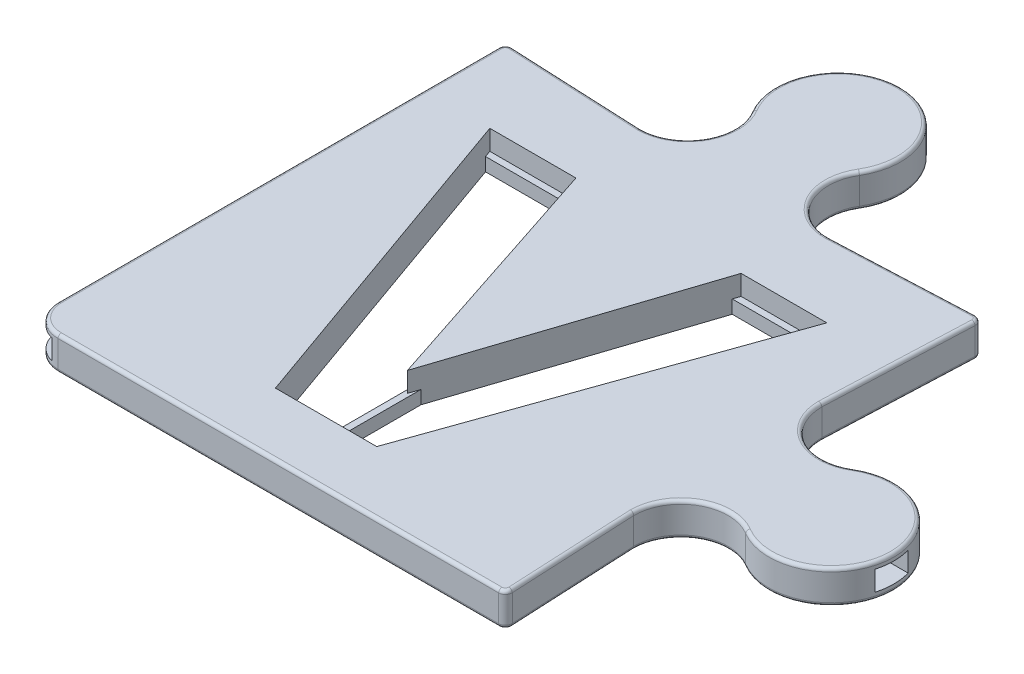
SolidWorks part; units mm, degrees
ref_plane "Front Plane" through (0, 0, 0) normal (0, 0, 1) x (1, 0, 0)
ref_plane "Top Plane" through (0, 0, 0) normal (0, 1, 0) x (1, 0, 0)
ref_plane "Right Plane" through (0, 0, 0) normal (1, 0, 0) x (0, 0, -1)
sketch "Sketch1" plane through (0, 0, 0) normal (0, 1, 0) x (1, 0, 0)
  line L0 (-31, -36) -> (37, -36) construction
  line L1 (-36, 37) -> (-36, -31) construction
  line L2 (-14.1421, 36) -> (-36, 37) construction
  line L3 (37, 37) -> (14.1421, 36) construction
  line L4 (36, 13.1421) -> (37, 37) construction
  line L5 (37, -36) -> (36, -15.1421) construction
  line L6 (-35.4, 36.3719) -> (-35.4, -31)
  line L7 (-36, 36) -> (36, 36) construction
  line L8 (-36, 36) -> (-36, -36) construction
  line L9 (-36, -36) -> (36, -36) construction
  line L10 (36, 36) -> (36, -36) construction
  line L11 (-31, -35.4) -> (36.3705, -35.4)
  line L12 (36.3705, -35.4) -> (35.4, -15.1568)
  line L13 (35.4, 13.155) -> (36.3732, 36.372)
  line L14 (36.3732, 36.372) -> (14.1555, 35.4)
  line L15 (-14.1562, 35.4) -> (-35.4, 36.3719)
  line L16 (-30, -24) -> (30, -24) construction
  line L17 (-30, 29) -> (30, 29) construction
  line L18 (-30, 29) -> (-30, -31) construction
  line L19 (-30, -31) -> (30, -31) construction
  line L20 (30, 29) -> (30, -31) construction
  line L21 (-30, 24) -> (30, 24) construction
  line L22 (-30, 24) -> (-30, -26) construction
  line L23 (-30, -26) -> (30, -26) construction
  line L24 (30, 24) -> (30, -26) construction
  arc A0 (-36, -31) -> (-31, -36) centre (-31, -31) ccw construction
  arc A1 (-14.1421, 36) -> (-8.571, 45.8485) centre (-14.1421, 42.5) ccw construction
  arc A2 (8.571, 45.8485) -> (-8.571, 45.8485) centre (0, 51) ccw construction
  arc A3 (8.571, 45.8485) -> (14.1421, 36) centre (14.1421, 42.5) ccw construction
  arc A4 (36, 13.1421) -> (45.8485, 7.571) centre (42.5, 13.1421) ccw construction
  arc A5 (45.8485, -9.571) -> (45.8485, 7.571) centre (51, -1) ccw construction
  arc A6 (45.8485, -9.571) -> (36, -15.1421) centre (42.5, -15.1421) ccw construction
  arc A7 (-35.4, -31) -> (-31, -35.4) centre (-31, -31) ccw
  arc A8 (46.1576, -9.0567) -> (35.4, -15.1568) centre (42.5, -15.1421) ccw
  arc A9 (46.1576, -9.0567) -> (46.1576, 7.0567) centre (51, -1) ccw
  arc A10 (35.4, 13.155) -> (46.1576, 7.0567) centre (42.5, 13.1421) ccw
  arc A11 (8.0567, 46.1576) -> (14.1555, 35.4) centre (14.1421, 42.5) ccw
  arc A12 (8.0567, 46.1576) -> (-8.0567, 46.1576) centre (0, 51) ccw
  arc A13 (-14.1562, 35.4) -> (-8.0567, 46.1576) centre (-14.1421, 42.5) ccw
  point P28 (0, 0)
  point P32 (36, 0)
  point P34 (0, 36)
  dimension "D5" = 6.5
  dimension "D6" = 10
  dimension "D7" = 6.5
  dimension "D13" = 5
  dimension "D9" = 10
  dimension "D11" = 6.5
  dimension "D12" = 6.5
  dimension "D1" = 72
  dimension "D2" = 1
  dimension "D3" = 1
  dimension "D4" = 15
  dimension "D8" = 1
  dimension "D10" = 35
  dimension "D14" = 15
  dimension "D15" = 36
  dimension "D16" = 1
  dimension "D18" = 60
  dimension "D19" = 60
  dimension "D20" = 5
  dimension "D21" = 6
  dimension "D22" = 5
  dimension "D23" = 50
  dimension "D24" = 2
  dimension "D17" = 0.6
extrude "Boss-Extrude1" add sketch "Sketch1" along normal blind 5
sketch "Sketch6" plane through (0, 0, 0) normal (0, -1, 0) x (1, 0, 0)
  line L0 (-35.4, -36.3719) -> (-35.4, 31) construction
  line L1 (-35.4, 17.9) -> (-27.4, 17.9)
  line L2 (-35.4, 17.9) -> (-35.4, -16.1)
  line L3 (-35.4, -16.1) -> (-27.4, -16.1)
  line L4 (-27.4, 17.9) -> (-27.4, -16.1)
  line L5 (-31, 35.4) -> (36.3705, 35.4) construction
  line L6 (-35.4, 14.65) -> (-30.4, 14.65)
  line L7 (-35.4, 14.65) -> (-35.4, -12.85)
  line L8 (-35.4, -12.85) -> (-30.4, -12.85)
  line L9 (-30.4, 14.65) -> (-30.4, -12.85)
  point P15 (-27.4, 0.9)
  point P16 (-30.4, 0.9)
  line M28 (-35.4, 31) -> (-35.4, -36.3719)
  dimension "D1" = 8
  dimension "D2" = 20.75
  dimension "D3" = 27.5
  dimension "D4" = 5
  dimension "D5" = 34
extrude "Cut-Extrude3" cut sketch "Sketch6" against normal blind 3 from offset 1 contours L6 L9 L8 L3 L4 L1 M28 | L9 L6 L2 L8 region at (-29.8665, 0, 0.9) region at (-32.9, 0, 0.9) offset against normal yes
extrude "Cut-Extrude4" cut sketch "Sketch6<3>" against normal up to next contours L9 L6 L2 L8 region at (-32.9, 0, 0.9)
sketch "Sketch6<3>" plane through (0, 0, 0) normal (0, -1, 0) x (1, 0, 0) same geometry as "Sketch6"
sketch "Sketch8" plane through (0, 0, 0) normal (0, -1, 0) x (1, 0, 0)
  line L1 (-2.5, -51.4) -> (2.5, -51.4)
  line L2 (-2.5, -51.4) -> (-2.5, -60.4)
  line L3 (-2.5, -60.4) -> (2.5, -60.4)
  line L4 (2.5, -51.4) -> (2.5, -60.4)
  line L5 (51.4, 3.5) -> (60.4, 3.5)
  line L6 (51.4, 3.5) -> (51.4, -1.5)
  line L7 (51.4, -1.5) -> (60.4, -1.5)
  line L8 (60.4, 3.5) -> (60.4, -1.5)
  arc A0 (-8.0567, -46.1576) -> (8.0567, -46.1576) centre (0, -51) ccw construction
  arc A1 (46.1576, -7.0567) -> (46.1576, 9.0567) centre (51, 1) ccw construction
  point P4 (0, -60.4)
  point P13 (60.4, 1)
  dimension "D1" = 5
  dimension "D2" = 9
  dimension "D3" = 5
  dimension "D4" = 9
extrude "Cut-Extrude5" cut sketch "Sketch8" against normal blind 3 from offset 1 offset against normal yes
sketch "Sketch9" plane through (0, 0, 0) normal (0, -1, 0) x (1, 0, 0)
  line L0 (-31, 35.4) -> (36.3705, 35.4) construction
  line L1 (-35.4, 14.65) -> (-35.4, 31) construction
  line L2 (-31.7636, 35.3332) -> (-35.4, 31) construction
  line L3 (-33.2571, 29.735) -> (-30.0429, 33.565) construction
  line L4 (-30.0429, 33.565) -> (-33.2571, 29.735) construction
  line L5 (-30.0429, 33.565) -> (-32.7119, 35.8048)
  line L6 (-33.2571, 29.735) -> (-35.926, 31.9747)
  line L7 (-32.7119, 35.8048) -> (-35.926, 31.9747)
  circle A0 centre (-31.65, 31.65) radius 2.5
  arc A1 (-31, 35.4) -> (-35.4, 31) centre (-31, 31) ccw construction
  arc M41 (-31, 35.4) -> (-35.4, 31) centre (-31, 31) ccw
  dimension "D1" = 5
  dimension "D3" = 3.75
  dimension "D4" = 5.6569
  dimension "D2" = 3.75
extrude "Cut-Extrude6" cut sketch "Sketch9" against normal blind 3 from offset 1 contours A0 L5 L6 M41 | A0 L5 region at (-33.6239, 0, 33.3064) region at (-31.65, 0, 31.65) offset against normal yes
sketch "Sketch11" plane through (-35.4, 0, 0) normal (-1, 0, 0) x (0, 0, 1)
  line L0 (-13.155, 0) -> (-36.372, 0) construction
  line L1 (-25.1, 3) -> (-19.1, 3)
  line L2 (-25.1, 3) -> (-25.1, 1.5)
  line L3 (-25.1, 1.5) -> (-19.1, 1.5)
  line L4 (-19.1, 3) -> (-19.1, 1.5)
  line L5 (-16.1, 4) -> (-16.1, 1) construction
  line L6 (35.4, 0) -> (15.1568, 0) construction
  line L7 (20.9, 3) -> (26.9, 3)
  line L8 (20.9, 3) -> (20.9, 1.5)
  line L9 (20.9, 1.5) -> (26.9, 1.5)
  line L10 (26.9, 3) -> (26.9, 1.5)
  line L12 (17.9, 4) -> (17.9, 1) construction
  dimension "D1" = 3
  dimension "D2" = 1.5
  dimension "D3" = 3
  dimension "D4" = 6
  dimension "D5" = 3
  dimension "D6" = 1.5
  dimension "D7" = 6
  dimension "D8" = 3
fillet "Fillet1" radius 0.5 17 edges at (-35.4, 0, 22.825) (-34.1113, 0, 34.1113) (2.6853, 0, 35.4) (35.8853, 0, 25.2784) (38.9978, 0, 8.966) (60.4, 0, 1) (38.9986, 0, -6.9655) (35.8866, 0, -24.7635) (25.2643, 0, -35.886) (7.9657, 0, -38.9984) (0, 0, -60.4) (-7.9658, 0, -38.9981) (-24.7781, 0, -35.886) (-35.4, 0, -24.611) (-32.9, 0, -12.85) (-30.4, 0, 0.9) (-32.9, 0, 14.65)
fillet "Fillet2" radius 0.5 13 edges at (-7.9658, 5, -38.9981) (0, 5, -60.4) (7.9657, 5, -38.9984) (25.2643, 5, -35.886) (35.8866, 5, -24.7635) (38.9986, 5, -6.9655) (60.4, 5, 1) (38.9978, 5, 8.966) (35.8853, 5, 25.2784) (2.6853, 5, 35.4) (-34.1113, 5, 34.1113) (-35.4, 5, -2.686) (-24.7781, 5, -35.886)
fillet "Fillet3" radius 1 9 edges at (36.2202, 0.1464, -36.2187) (36.2202, 4.8536, -36.2187) (36.3732, 2.5, -36.372) (-35.2536, 0.1464, -36.2186) (-35.2536, 4.8536, -36.2186) (36.2169, 0.1464, 35.2536) (36.2169, 4.8536, 35.2536) (36.3705, 2.5, 35.4) (-35.4, 2.5, -36.3719)
extrude "Cut-Extrude9" cut sketch "Sketch11" against normal blind 3
chamfer "Chamfer1" distance 1 angle 50 2 edges at (-35.4, 1.5, 23.9) (-35.4, 1.5, -22.1) first distance on face at (-35.4, 2.25, -22.1)
sketch "Sketch12" plane through (0, 5, 0) normal (0, 1, 0) x (1, 0, 0)
  text T0 "V" font "Poppins" height 50
extrude "Cut-Extrude10" cut sketch "Sketch12" against normal through all
sketch "Sketch13" plane through (0, 0, 0) normal (0, -1, 0) x (1, 0, 0)
  line L0 (-7.6772, 26) -> (-25.4122, -24) construction
  line L1 (-8.0319, 25) -> (7.9188, 25)
  line L2 (-8.0319, 25) -> (-8.0319, 26)
  line L3 (-8.0319, 26) -> (7.9188, 26)
  line L4 (7.9188, 25) -> (7.9188, 26)
  line L5 (-12.4485, -24) -> (-0.0515, 13.7473) construction
  line L6 (-0.5503, 12.2287) -> (0.4497, 12.2287)
  line L7 (-0.5503, 12.2287) -> (-0.5503, 26)
  line L8 (-0.5503, 26) -> (0.4497, 26)
  line L9 (0.4497, 12.2287) -> (0.4497, 26)
  line L10 (-0.0515, 13.7473) -> (12.4073, -24) construction
  line L11 (-12.1201, -23) -> (-25.4122, -23)
  line L12 (-12.1201, -23) -> (-12.1201, -24)
  line L13 (-12.1201, -24) -> (-25.4122, -24)
  line L14 (-25.4122, -23) -> (-25.4122, -24)
  line L15 (12.0772, -23) -> (25.3092, -23)
  line L16 (12.0772, -23) -> (12.0772, -24)
  line L17 (12.0772, -24) -> (25.3092, -24)
  line L18 (25.3092, -23) -> (25.3092, -24)
  line L19 (7.5639, 26) -> (-7.6772, 26) construction
  line L20 (25.3092, -24) -> (7.5639, 26) construction
  point P24 (1.2767, 9.7232)
  point P25 (-8.2229, 25.458)
  point P26 (1.2145, 26)
  point P29 (0, 0)
  point P30 (8.1058, 24.4732)
  line M31 (25.3092, -24) -> (12.4073, -24)
  line M32 (12.4073, -24) -> (-0.0515, 13.7473)
  line M33 (-0.0515, 13.7473) -> (-12.4485, -24)
  line M34 (-12.4485, -24) -> (-25.4122, -24)
  line M35 (-25.4122, -24) -> (-7.6772, 26)
  line M37 (7.5639, 26) -> (25.3092, -24)
  dimension "D1" = 1
  dimension "D2" = 1
  dimension "D3" = 1
  dimension "D4" = 1
extrude "Boss-Extrude2" add sketch "Sketch13" against normal blind 2 contours L11 M33 M35 M34 | L15 M32 M31 M37 | L1 L4 L3 L2 | L9 L8 L7 L6 region at (-18.7596, 0, -23.5002) region at (18.687, 0, -23.5002)
